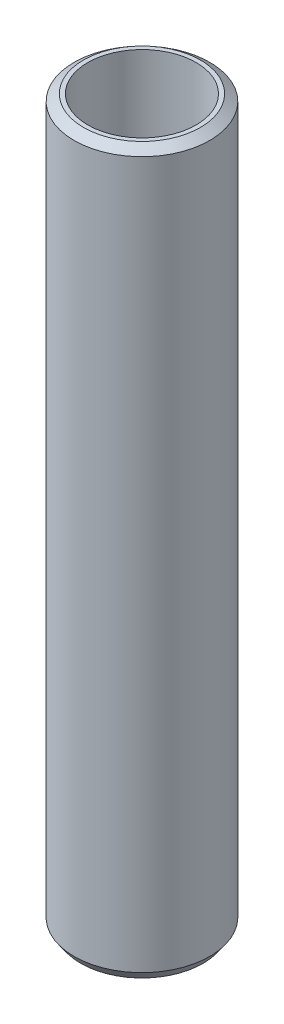
SolidWorks part; units mm, degrees
ref_plane "Front Plane" through (0, 0, 0) normal (0, 0, 1) x (1, 0, 0)
ref_plane "Top Plane" through (0, 0, 0) normal (0, 1, 0) x (1, 0, 0)
ref_plane "Right Plane" through (0, 0, 0) normal (1, 0, 0) x (0, 0, -1)
sketch "Sketch1" plane through (0, 0, 0) normal (0, 1, 0) x (1, 0, 0)
  circle A0 centre (0, 0) radius 50
  dimension "SHAFT_OD" = 100
extrude "Boss-Extrude1" add sketch "Sketch1" along normal blind 532.9778
sketch "Sketch2" plane through (0, 0, 0) normal (0, 1, 0) x (1, 0, 0)
  circle A0 centre (0, 0) radius 39.9432
  dimension "BORE_D" = 79.8863
extrude "Cut-Extrude1" cut sketch "Sketch2" along normal through all
chamfer "Chamfer1" distance 4.883 angle 54.618 2 edges at (0, 532.9778, 50) (0, 0, 50) first distance on face at (0, 532.9778, 50) first distance on face at (0, 0, 39.9432)
